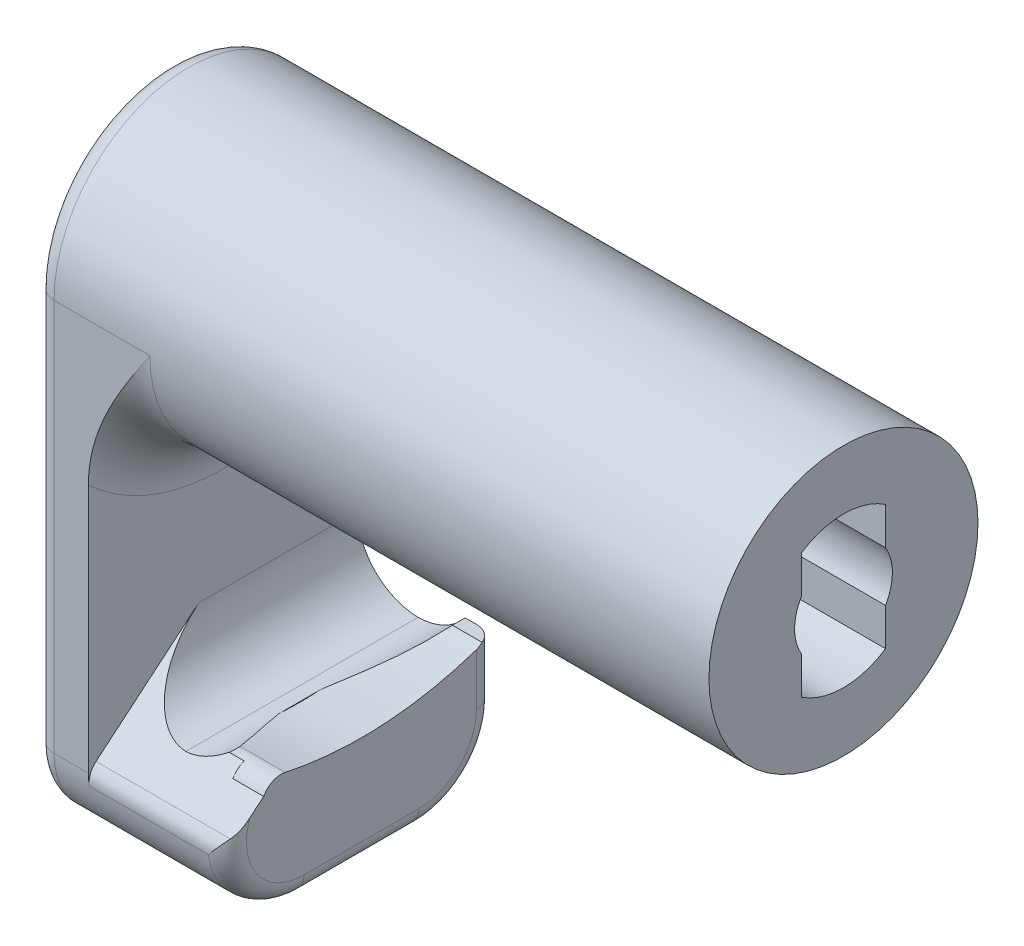
SolidWorks part; units mm, degrees
material "ABS"
ref_plane "Front Plane" through (0, 0, 0) normal (1, 0, 0) x (0, 1, 0)
ref_plane "Top Plane" through (0, 0, 0) normal (0, 0, 1) x (0, 1, 0)
ref_plane "Right Plane" through (0, 0, 0) normal (0, 1, 0) x (-1, 0, 0)
sketch "Sketch1" plane through (0, 0, 0) normal (1, 0, 0) x (0, 1, 0)
  circle A0 centre (0, 0) radius 3.175
  circle A1 centre (0, 0) radius 3
  circle A2 centre (0, 0) radius 8.7376
  dimension "D1" = 6
  dimension "D2" = 6.35
  dimension "D3" = 17.4752
extrude "Boss-Extrude1" add sketch "Sketch1" along normal blind 43.8052 contours A2 A0 region at (0, -8.4905, 0)
extrude "Boss-Extrude2" add sketch "Sketch1<3>" along normal blind 7 contours A0 A1 region at (0, -3.0852, 0)
sketch "Sketch1<3>" plane through (0, 0, 0) normal (1, 0, 0) x (0, 1, 0) same geometry as "Sketch1"
sketch "Sketch10" plane through (0, 0, 0) normal (-1, 0, 0) x (0, -1, 0)
  line L0 (0, 8.7376) -> (30.48, 8.7376)
  line L2 (30.48, 8.7376) -> (30.48, -8.7376)
  line L3 (30.48, -8.7376) -> (0, -8.7376)
  circle A0 centre (0, 0) radius 8.7376 construction
  arc A2 (0, 8.7376) -> (0, -8.7376) centre (0, 0) cw
  dimension "D1" = 30.48
extrude "Boss-Extrude3" add sketch "Sketch10" against normal blind 3.5 contours L0 A2 L3 L2 region at (0, -18.5907, 0)
fillet "Fillet2" radius 5 2 edges at (1.75, -30.48, 8.7376) (1.75, -30.48, -8.7376)
sketch "Sketch14" plane through (0, 0, 0) normal (-1, 0, 0) x (0, 0, 1)
  line L0 (0.5115, -3.4237) -> (0.3944, -4.0089)
  line L1 (0, 0) -> (0, -4.064) construction
  line L2 (0, 0) -> (0.5606, -3.4335) construction
  line L3 (0.6039, -3.4087) -> (0.9011, -3.9262)
  line L4 (-0.6903, -3.3922) -> (-1.0005, -3.9021)
  line L5 (-0.5983, -3.4096) -> (-0.4961, -3.9976)
  line L6 (-1.8089, -2.9515) -> (-2.2748, -3.3245)
  line L7 (-1.7284, -2.9994) -> (-1.8334, -3.5869)
  line L8 (-2.7093, -2.1549) -> (-3.2746, -2.346)
  line L9 (-2.65, -2.2273) -> (-2.9496, -2.7435)
  line L10 (-3.2829, -1.0983) -> (-3.8795, -1.0846)
  line L11 (-3.252, -1.1867) -> (-3.7101, -1.5692)
  line L12 (-3.4605, 0.0907) -> (-4.0165, 0.3077)
  line L13 (-3.4617, -0.0029) -> (-4.023, -0.2057)
  line L14 (-3.2208, 1.2689) -> (-3.669, 1.6629)
  line L15 (-3.2539, 1.1813) -> (-3.8507, 1.1827)
  line L16 (-2.5926, 2.2939) -> (-2.879, 2.8175)
  line L17 (-2.6537, 2.223) -> (-3.214, 2.4284)
  line L18 (-1.6517, 3.0423) -> (-1.7417, 3.6323)
  line L19 (-1.7333, 2.9965) -> (-2.1896, 3.3812)
  line L20 (-0.5115, 3.4237) -> (-0.3944, 4.0089)
  line L21 (-0.6039, 3.4087) -> (-0.9011, 3.9262)
  line L22 (0.6903, 3.3922) -> (1.0005, 3.9021)
  line L23 (0.5983, 3.4096) -> (0.4961, 3.9976)
  line L24 (1.8089, 2.9515) -> (2.2748, 3.3245)
  line L25 (1.7284, 2.9994) -> (1.8334, 3.5869)
  line L26 (2.7093, 2.1549) -> (3.2746, 2.346)
  line L27 (2.65, 2.2273) -> (2.9496, 2.7435)
  line L28 (3.2829, 1.0983) -> (3.8795, 1.0846)
  line L29 (3.252, 1.1867) -> (3.7101, 1.5692)
  line L30 (3.4605, -0.0907) -> (4.0165, -0.3077)
  line L31 (3.4617, 0.0029) -> (4.023, 0.2057)
  line L32 (3.2208, -1.2689) -> (3.669, -1.6629)
  line L33 (3.2539, -1.1813) -> (3.8507, -1.1827)
  line L34 (2.5926, -2.2939) -> (2.879, -2.8175)
  line L35 (2.6537, -2.223) -> (3.214, -2.4284)
  line L36 (1.6517, -3.0423) -> (1.7417, -3.6323)
  line L37 (1.7333, -2.9965) -> (2.1896, -3.3812)
  line L38 (-0.1032, -4.0627) -> (0, -4.064)
  line L39 (-1.4865, -3.7824) -> (-1.39, -3.8189)
  line L40 (-2.6905, -3.0459) -> (-2.6123, -3.1132)
  line L41 (-3.5195, -2.032) -> (-3.57, -1.942)
  line L42 (-4.0023, -0.7057) -> (-4.0189, -0.6039)
  line L43 (-4.0023, 0.7057) -> (-3.9831, 0.8071)
  line L44 (-3.5195, 2.032) -> (-3.4668, 2.1207)
  line L45 (-2.6123, 3.1132) -> (-2.5324, 3.1785)
  line L46 (-1.39, 3.8189) -> (-1.2926, 3.853)
  line L47 (0, 4.064) -> (0.1032, 4.0627)
  line L48 (1.39, 3.8189) -> (1.4865, 3.7824)
  line L49 (2.6123, 3.1132) -> (2.6905, 3.0459)
  line L50 (3.5195, 2.032) -> (3.57, 1.942)
  line L51 (4.0023, 0.7057) -> (4.0189, 0.6039)
  line L52 (4.0023, -0.7057) -> (3.9831, -0.8071)
  line L53 (3.5195, -2.032) -> (3.4668, -2.1207)
  line L54 (2.6123, -3.1132) -> (2.5324, -3.1785)
  line L55 (1.39, -3.8189) -> (1.2926, -3.853)
  arc A0 (0.3497, -4.0489) -> (0, -4.064) centre (0, 0) cw
  arc A1 (0.3497, -4.0489) -> (0.3944, -4.0089) centre (0.3454, -3.9991) ccw
  arc A2 (0.5115, -3.4237) -> (0.6039, -3.4087) centre (0.5606, -3.4335) cw
  arc A3 (0.4203, -4.0631) -> (0.3944, -4.0089) centre (0.4434, -4.0187) cw
  arc A4 (0.4203, -4.0631) -> (0.7372, -4.2116) centre (2.3016, -0.4608) ccw
  arc A6 (0.9562, -3.9499) -> (0.9011, -3.9262) centre (0.9445, -3.9013) cw
  arc A7 (0.9562, -3.9499) -> (1.2926, -3.853) centre (0, 0) ccw
  arc A8 (-1.0562, -3.9243) -> (-1.39, -3.8189) centre (0, 0) cw
  arc A9 (-1.0562, -3.9243) -> (-1.0005, -3.9021) centre (-1.0432, -3.8761) ccw
  arc A10 (-0.6903, -3.3922) -> (-0.5983, -3.4096) centre (-0.6476, -3.4182) cw
  arc A11 (-0.4524, -4.0387) -> (-0.4961, -3.9976) centre (-0.4468, -3.9891) cw
  arc A12 (-0.4524, -4.0387) -> (-0.1032, -4.0627) centre (0, 0) ccw
  arc A13 (-2.3347, -3.3264) -> (-2.6123, -3.1132) centre (0, 0) cw
  arc A14 (-2.3347, -3.3264) -> (-2.2748, -3.3245) centre (-2.306, -3.2855) ccw
  arc A15 (-1.8089, -2.9515) -> (-1.7284, -2.9994) centre (-1.7776, -2.9906) cw
  arc A16 (-1.8064, -3.6405) -> (-1.8334, -3.5869) centre (-1.7842, -3.5957) cw
  arc A17 (-1.8064, -3.6405) -> (-1.4865, -3.7824) centre (0, 0) ccw
  arc A18 (-3.3316, -2.3273) -> (-3.5195, -2.032) centre (0, 0) cw
  arc A19 (-3.3316, -2.3273) -> (-3.2746, -2.346) centre (-3.2906, -2.2987) ccw
  arc A20 (-2.7093, -2.1549) -> (-2.65, -2.2273) centre (-2.6933, -2.2022) cw
  arc A21 (-2.9426, -2.8031) -> (-2.9496, -2.7435) centre (-2.9064, -2.7686) cw
  arc A22 (-2.9426, -2.8031) -> (-2.6905, -3.0459) centre (0, 0) ccw
  arc A23 (-3.9267, -1.0475) -> (-4.0023, -0.7057) centre (0, 0) cw
  arc A24 (-3.9267, -1.0475) -> (-3.8795, -1.0846) centre (-3.8784, -1.0346) ccw
  arc A25 (-3.2829, -1.0983) -> (-3.252, -1.1867) centre (-3.284, -1.1483) cw
  arc A26 (-3.7238, -1.6276) -> (-3.7101, -1.5692) centre (-3.678, -1.6076) cw
  arc A27 (-3.7238, -1.6276) -> (-3.57, -1.942) centre (0, 0) ccw
  arc A28 (-4.0481, 0.3587) -> (-4.0023, 0.7057) centre (0, 0) cw
  arc A29 (-4.0481, 0.3587) -> (-4.0165, 0.3077) centre (-3.9983, 0.3543) ccw
  arc A30 (-3.4605, 0.0907) -> (-3.4617, -0.0029) centre (-3.4787, 0.0442) cw
  arc A31 (-4.0559, -0.2558) -> (-4.023, -0.2057) centre (-4.006, -0.2527) cw
  arc A32 (-4.0559, -0.2558) -> (-4.0189, -0.6039) centre (0, 0) ccw
  arc A33 (-3.6813, 1.7216) -> (-3.5195, 2.032) centre (0, 0) cw
  arc A34 (-3.6813, 1.7216) -> (-3.669, 1.6629) centre (-3.636, 1.7005) ccw
  arc A35 (-3.2208, 1.2689) -> (-3.2539, 1.1813) centre (-3.2538, 1.2313) cw
  arc A36 (-3.8988, 1.1468) -> (-3.8507, 1.1827) centre (-3.8509, 1.1327) cw
  arc A37 (-3.8988, 1.1468) -> (-3.9831, 0.8071) centre (0, 0) ccw
  arc A38 (-2.8705, 2.8769) -> (-2.6123, 3.1132) centre (0, 0) cw
  arc A39 (-2.8705, 2.8769) -> (-2.879, 2.8175) centre (-2.8352, 2.8415) ccw
  arc A40 (-2.5926, 2.2939) -> (-2.6537, 2.223) centre (-2.6365, 2.2699) cw
  arc A41 (-3.2715, 2.4111) -> (-3.214, 2.4284) centre (-3.2312, 2.3815) cw
  arc A42 (-3.2715, 2.4111) -> (-3.4668, 2.1207) centre (0, 0) ccw
  arc A43 (-1.7134, 3.6852) -> (-1.39, 3.8189) centre (0, 0) cw
  arc A44 (-1.7134, 3.6852) -> (-1.7417, 3.6323) centre (-1.6923, 3.6398) ccw
  arc A45 (-1.6517, 3.0423) -> (-1.7333, 2.9965) centre (-1.7011, 3.0348) cw
  arc A46 (-2.2495, 3.3846) -> (-2.1896, 3.3812) centre (-2.2218, 3.343) cw
  arc A47 (-2.2495, 3.3846) -> (-2.5324, 3.1785) centre (0, 0) ccw
  arc A48 (-0.3497, 4.0489) -> (0, 4.064) centre (0, 0) cw
  arc A49 (-0.3497, 4.0489) -> (-0.3944, 4.0089) centre (-0.3454, 3.9991) ccw
  arc A50 (-0.5115, 3.4237) -> (-0.6039, 3.4087) centre (-0.5606, 3.4335) cw
  arc A51 (-0.9562, 3.9499) -> (-0.9011, 3.9262) centre (-0.9445, 3.9013) cw
  arc A52 (-0.9562, 3.9499) -> (-1.2926, 3.853) centre (0, 0) ccw
  arc A53 (1.0562, 3.9243) -> (1.39, 3.8189) centre (0, 0) cw
  arc A54 (1.0562, 3.9243) -> (1.0005, 3.9021) centre (1.0432, 3.8761) ccw
  arc A55 (0.6903, 3.3922) -> (0.5983, 3.4096) centre (0.6476, 3.4182) cw
  arc A56 (0.4524, 4.0387) -> (0.4961, 3.9976) centre (0.4468, 3.9891) cw
  arc A57 (0.4524, 4.0387) -> (0.1032, 4.0627) centre (0, 0) ccw
  arc A58 (2.3347, 3.3264) -> (2.6123, 3.1132) centre (0, 0) cw
  arc A59 (2.3347, 3.3264) -> (2.2748, 3.3245) centre (2.306, 3.2855) ccw
  arc A60 (1.8089, 2.9515) -> (1.7284, 2.9994) centre (1.7776, 2.9906) cw
  arc A61 (1.8064, 3.6405) -> (1.8334, 3.5869) centre (1.7842, 3.5957) cw
  arc A62 (1.8064, 3.6405) -> (1.4865, 3.7824) centre (0, 0) ccw
  arc A63 (3.3316, 2.3273) -> (3.5195, 2.032) centre (0, 0) cw
  arc A64 (3.3316, 2.3273) -> (3.2746, 2.346) centre (3.2906, 2.2987) ccw
  arc A65 (2.7093, 2.1549) -> (2.65, 2.2273) centre (2.6933, 2.2022) cw
  arc A66 (2.9426, 2.8031) -> (2.9496, 2.7435) centre (2.9064, 2.7686) cw
  arc A67 (2.9426, 2.8031) -> (2.6905, 3.0459) centre (0, 0) ccw
  arc A68 (3.9267, 1.0475) -> (4.0023, 0.7057) centre (0, 0) cw
  arc A69 (3.9267, 1.0475) -> (3.8795, 1.0846) centre (3.8784, 1.0346) ccw
  arc A70 (3.2829, 1.0983) -> (3.252, 1.1867) centre (3.284, 1.1483) cw
  arc A71 (3.7238, 1.6276) -> (3.7101, 1.5692) centre (3.678, 1.6076) cw
  arc A72 (3.7238, 1.6276) -> (3.57, 1.942) centre (0, 0) ccw
  arc A73 (4.0481, -0.3587) -> (4.0023, -0.7057) centre (0, 0) cw
  arc A74 (4.0481, -0.3587) -> (4.0165, -0.3077) centre (3.9983, -0.3543) ccw
  arc A75 (3.4605, -0.0907) -> (3.4617, 0.0029) centre (3.4787, -0.0442) cw
  arc A76 (4.0559, 0.2558) -> (4.023, 0.2057) centre (4.006, 0.2527) cw
  arc A77 (4.0559, 0.2558) -> (4.0189, 0.6039) centre (0, 0) ccw
  arc A78 (3.6813, -1.7216) -> (3.5195, -2.032) centre (0, 0) cw
  arc A79 (3.6813, -1.7216) -> (3.669, -1.6629) centre (3.636, -1.7005) ccw
  arc A80 (3.2208, -1.2689) -> (3.2539, -1.1813) centre (3.2538, -1.2313) cw
  arc A81 (3.8988, -1.1468) -> (3.8507, -1.1827) centre (3.8509, -1.1327) cw
  arc A82 (3.8988, -1.1468) -> (3.9831, -0.8071) centre (0, 0) ccw
  arc A83 (2.8705, -2.8769) -> (2.6123, -3.1132) centre (0, 0) cw
  arc A84 (2.8705, -2.8769) -> (2.879, -2.8175) centre (2.8352, -2.8415) ccw
  arc A85 (2.5926, -2.2939) -> (2.6537, -2.223) centre (2.6365, -2.2699) cw
  arc A86 (3.2715, -2.4111) -> (3.214, -2.4284) centre (3.2312, -2.3815) cw
  arc A87 (3.2715, -2.4111) -> (3.4668, -2.1207) centre (0, 0) ccw
  arc A88 (1.7134, -3.6852) -> (1.39, -3.8189) centre (0, 0) cw
  arc A89 (1.7134, -3.6852) -> (1.7417, -3.6323) centre (1.6923, -3.6398) ccw
  arc A90 (1.6517, -3.0423) -> (1.7333, -2.9965) centre (1.7011, -3.0348) cw
  arc A91 (2.2495, -3.3846) -> (2.1896, -3.3812) centre (2.2218, -3.343) cw
  arc A92 (2.2495, -3.3846) -> (2.5324, -3.1785) centre (0, 0) ccw
  point P207 (0, 0)
  dimension "D1" = 4.064
  dimension "D2" = 0.05
  dimension "D3" = 0.05
  dimension "D4" = 0.04
  dimension "D5" = 18
  dimension "D6" = 0.5968
  dimension "D8" = 0.35
extrude "Cut-Extrude6" cut sketch "Sketch14" against normal blind 5.715 contours A91 A92 L54 A83 A84 L34 A85 L35 A86 A87 L53 A78 A79 L32 A80 L33 A81 A82 L52 A73 A74 L30 A75 L31 A76 A77 L51 A68 A69 L28 A70 L29 A71 A72 L50 A63 A64 L26 A65 L27 A66 A67 L49 A58 A59 L24 A60 L25 A61 A62 L48 region at (0, 0, 0)
sketch "Sketch15" plane through (3.5, 0, 0) normal (1, 0, 0) x (0, 1, 0)
  line L2 (-23.48, 6.35) -> (-23.48, -8.7376)
  line L5 (-30.48, 3.7376) -> (-30.48, -3.7376) construction
  line L6 (-30.48, 3.7376) -> (-30.48, -3.7376)
  line L7 (-23.48, 6.35) -> (-25.48, 8.7376)
  line L9 (-25.48, -8.7376) -> (0, -8.7376) construction
  line L13 (0, 8.7376) -> (-25.48, 8.7376)
  line L14 (-30.48, 3.7376) -> (-30.48, -3.7376)
  line L15 (-25.48, -8.7376) -> (0, -8.7376)
  line L16 (-23.48, 6.35) -> (-25.48, 8.7376)
  line L17 (-30.48, 3.7376) -> (-30.48, -3.7376)
  line L18 (-25.48, -8.7376) -> (-23.48, -8.7376)
  arc A0 (-25.48, 8.7376) -> (-30.48, 3.7376) centre (-25.48, 3.7376) ccw construction
  arc A1 (-30.48, -3.7376) -> (-25.48, -8.7376) centre (-25.48, -3.7376) ccw construction
  arc A2 (-25.48, 8.7376) -> (-30.48, 3.7376) centre (-25.48, 3.7376) ccw
  arc A3 (-30.48, -3.7376) -> (-25.48, -8.7376) centre (-25.48, -3.7376) ccw
  arc A7 (-25.48, 8.7376) -> (-30.48, 3.7376) centre (-25.48, 3.7376) ccw
  arc A8 (-30.48, -3.7376) -> (-25.48, -8.7376) centre (-25.48, -3.7376) ccw
  arc A9 (0, 8.7376) -> (0, -8.7376) centre (0, 0) ccw
  arc A10 (-25.48, 8.7376) -> (-30.48, 3.7376) centre (-25.48, 3.7376) ccw
  arc A11 (-30.48, -3.7376) -> (-25.48, -8.7376) centre (-25.48, -3.7376) ccw
  arc A12 (0, 8.7376) -> (0, -8.7376) centre (0, 0) ccw
  line M2 (0, 8.7376) -> (-25.48, 8.7376)
  arc M3 (-25.48, 8.7376) -> (-30.48, 3.7376) centre (-25.48, 3.7376) ccw
  line M4 (-30.48, 3.7376) -> (-30.48, -3.7376)
  arc M5 (-30.48, -3.7376) -> (-25.48, -8.7376) centre (-25.48, -3.7376) ccw
  dimension "D1" = 7
  dimension "D3" = 3.1146
  dimension "D2" = 0
extrude "Boss-Extrude4" add sketch "Sketch15" along normal blind 7 contours M2 M3 M4 M5 region at (3.5, -26.8078, -0.1736)
sketch "Sketch19" plane through (10.5, 0, 0) normal (1, 0, 0) x (0, 1, 0)
  line L23 (-23.48, 6.35) -> (-21.98, 6.35)
  line L25 (-21.98, 6.35) -> (-21.98, -8.7376)
  line L26 (-23.48, -8.7376) -> (0, -8.7376) construction
  line L27 (-23.48, -8.7376) -> (-23.48, 6.35)
  line L29 (-30.48, 3.7376) -> (-30.48, -3.7376)
  line L30 (-25.48, -8.7376) -> (-23.48, -8.7376)
  line L33 (-30.48, 3.7376) -> (-30.48, -3.7376)
  line L34 (-25.48, -8.7376) -> (-23.48, -8.7376)
  line L35 (-21.98, -8.7376) -> (-23.48, -8.7376)
  line L38 (-23.48, 6.35) -> (-25.48, 8.7376)
  line L39 (-23.48, 6.35) -> (-25.48, 8.7376)
  arc A6 (-25.48, 8.7376) -> (-30.48, 3.7376) centre (-25.48, 3.7376) ccw
  arc A7 (-30.48, -3.7376) -> (-25.48, -8.7376) centre (-25.48, -3.7376) ccw
  arc A8 (-25.48, 8.7376) -> (-30.48, 3.7376) centre (-25.48, 3.7376) ccw
  arc A9 (-30.48, -3.7376) -> (-25.48, -8.7376) centre (-25.48, -3.7376) ccw
  dimension "D2" = 8.5
  dimension "D1" = 0
extrude "Boss-Extrude7" add sketch "Sketch19" along normal blind 2
fillet "Fillet7" radius 4 3 edges at (10.5, -23.48, -1.1938) (3.5, -8.7376, 0) (3.5, -23.48, -1.1938)
sketch "Sketch21" plane through (12.5, 0, 0) normal (1, 0, 0) x (0, 1, 0)
  line L0 (-22.48, 6.35) -> (-21.98, 6.35)
  line L1 (-21.98, -8.7376) -> (-21.98, 6.35) construction
  line L2 (-21.98, -8.7376) -> (-21.98, 6.35)
  line L3 (-21.664, -8.7376) -> (-21.98, -8.7376)
  line L4 (-25.48, -8.7376) -> (-21.98, -8.7376) construction
  line L9 (-25.48, -8.7376) -> (-21.98, -8.7376)
  line L10 (-21.98, -8.7376) -> (-21.98, 6.35)
  line L11 (-21.98, 6.35) -> (-23.48, 6.35)
  line L12 (-30.48, 3.7376) -> (-30.48, -3.7376)
  line L13 (-25.48, -8.7376) -> (-21.98, -8.7376) construction
  line L14 (-21.98, -8.7376) -> (-21.98, 6.35) construction
  line L15 (-21.98, 6.35) -> (-23.48, 6.35) construction
  line L16 (-30.48, 3.7376) -> (-30.48, -3.7376) construction
  line L19 (-23.48, 6.35) -> (-25.48, 8.7376)
  line L20 (-23.48, 6.35) -> (-25.48, 8.7376)
  arc A2 (-21.664, -8.7376) -> (-22.48, 6.35) centre (0, 0) cw
  arc A5 (-25.48, 8.7376) -> (-30.48, 3.7376) centre (-25.48, 3.7376) ccw
  arc A6 (-30.48, -3.7376) -> (-25.48, -8.7376) centre (-25.48, -3.7376) ccw
  arc A7 (-25.48, 8.7376) -> (-30.48, 3.7376) centre (-25.48, 3.7376) ccw construction
  arc A8 (-30.48, -3.7376) -> (-25.48, -8.7376) centre (-25.48, -3.7376) ccw construction
  line M5 (-25.48, -8.7376) -> (-21.98, -8.7376)
  line M6 (-21.98, -8.7376) -> (-21.98, 6.35)
  line M7 (-21.98, 6.35) -> (-23.48, 6.35)
  dimension "D2" = 0.5
  dimension "D1" = 0
extrude "Cut-Extrude8" cut sketch "Sketch21" against normal blind 4 contours A2 M5 M6 M7 | L2 L0 A2 L3 region at (12.5, -22.5442, -0.196)
sketch "Sketch22" plane through (43.8052, 0, 0) normal (1, 0, 0) x (0, 1, 0)
  line L0 (-4.0561, 2.7305) -> (4.0561, 2.7305)
  line L1 (-4.0561, -2.7305) -> (4.0561, -2.7305)
  arc A0 (-4.0561, 2.7305) -> (-4.0561, -2.7305) centre (0, 0) ccw
  arc A1 (4.0561, -2.7305) -> (4.0561, 2.7305) centre (0, 0) ccw
  dimension "D1" = 9.779
  dimension "D2" = 5.461
extrude "Cut-Extrude10" cut sketch "Sketch22" against normal blind 12.192
fillet "Fillet8" radius 1.27 12 edges at (11.5, -22.48, 6.35) (0, -30.48, 0) (0, -29.0155, -7.2731) (0, -12.74, -8.7376) (0, 8.7376, 0) (0, -12.74, 8.7376) (12.5, -23.73, -8.7376) (12.5, -29.0155, -7.2731) (12.5, -30.48, 0) (0, -29.0155, 7.2731) (12.5, -29.0155, 7.2731) (8, -25.48, 8.7376)
